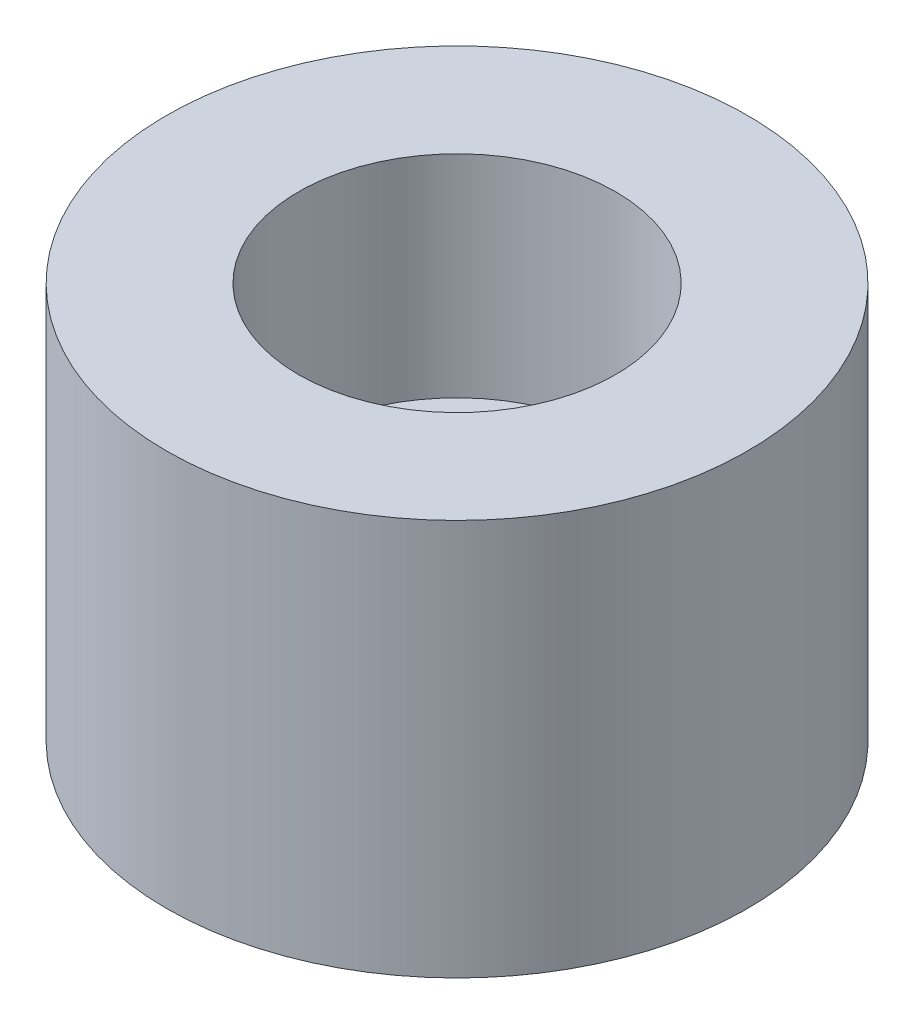
SolidWorks part; units mm, degrees
ref_plane "Front Plane" through (0, 0, 0) normal (0, 0, 1) x (1, 0, 0)
ref_plane "Top Plane" through (0, 0, 0) normal (0, 1, 0) x (1, 0, 0)
ref_plane "Right Plane" through (0, 0, 0) normal (1, 0, 0) x (0, 0, -1)
sketch "Sketch2" plane through (0, 0, 0) normal (0, 1, 0) x (1, 0, 0)
  circle A0 centre (0, 0) radius 11
  circle A1 centre (0, 0) radius 6
  dimension "D1" = 12
  dimension "D2" = 22
extrude "Boss-Extrude1" add sketch "Sketch2" along normal blind 15 contours A0
extrude "Cut-Extrude1" cut sketch "Sketch2<3>" against normal blind 8 from surface contours A1 starting at face at (0, 15, 11)
sketch "Sketch2<3>" plane through (0, 0, 0) normal (0, 1, 0) x (1, 0, 0) same geometry as "Sketch2"
